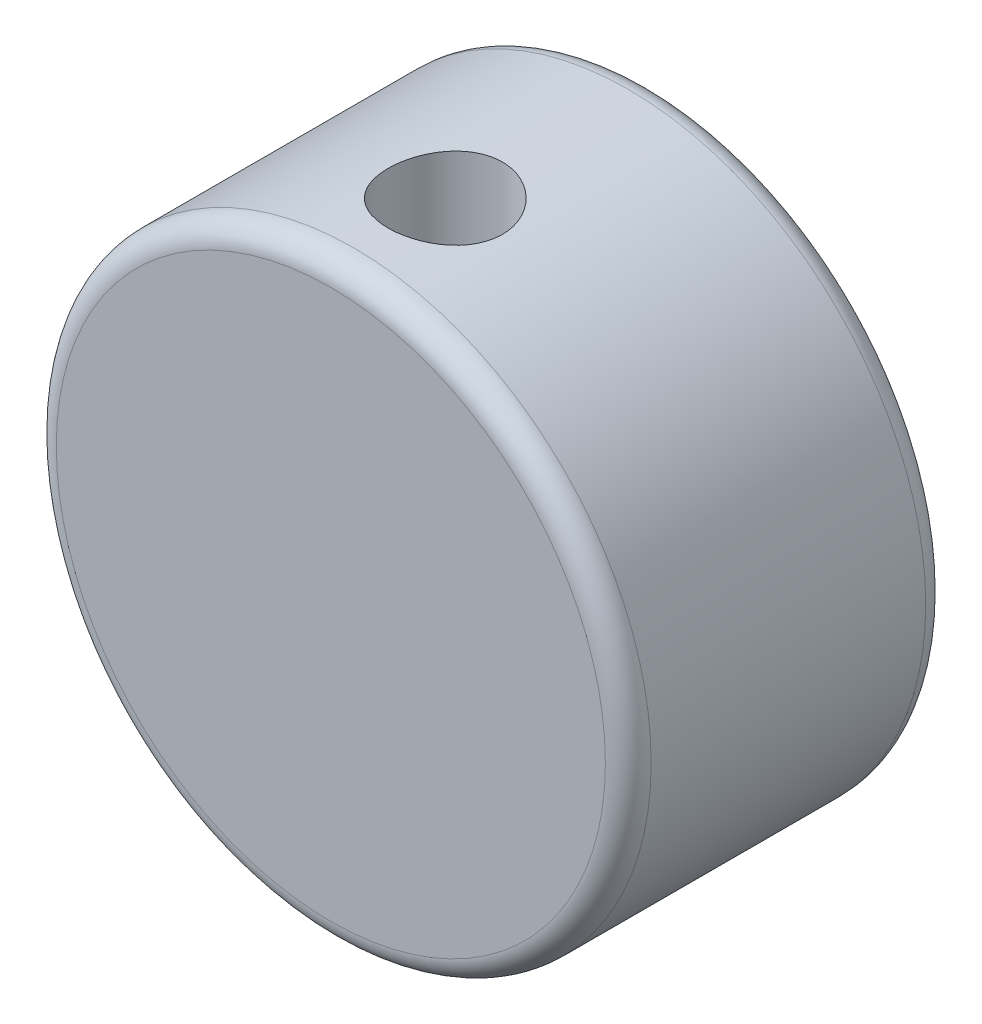
SolidWorks part; units mm, degrees
ref_plane "Front Plane" through (0, 0, 0) normal (0, 0, 1) x (1, 0, 0)
ref_plane "Top Plane" through (0, 0, 0) normal (0, 1, 0) x (1, 0, 0)
ref_plane "Right Plane" through (0, 0, 0) normal (1, 0, 0) x (0, 0, -1)
sketch "Sketch1" plane through (0, 0, 0) normal (0, 0, 1) x (1, 0, 0)
  circle A0 centre (0, 0) radius 65
  dimension "D1" = 130
extrude "Boss-Extrude1" add sketch "Sketch1" along normal blind 70
sketch "Sketch2" plane through (0, 0, 0) normal (0, 0, -1) x (-1, 0, 0)
  circle A0 centre (0, 0) radius 50
  dimension "D1" = 100
sketch "Sketch4" plane through (0, 0, 0) normal (0, 1, 0) x (1, 0, 0)
  circle A0 centre (0, -45) radius 12.5
  dimension "D1" = 25
  dimension "D2" = 45
extrude "Cut-Extrude3" cut sketch "Sketch4" against normal mid plane 133
extrude "Cut-Extrude4" cut sketch "Sketch2" against normal blind 10
sketch "Sketch5" plane through (0, 0, 10) normal (0, 0, -1) x (-1, 0, 0)
  circle A0 centre (0, 0) radius 60
extrude "Cut-Extrude5" cut sketch "Sketch5" against normal blind 10
fillet "Raccordo1" radius 5 2 edges at (65, 0, 0) (65, 0, 70)
